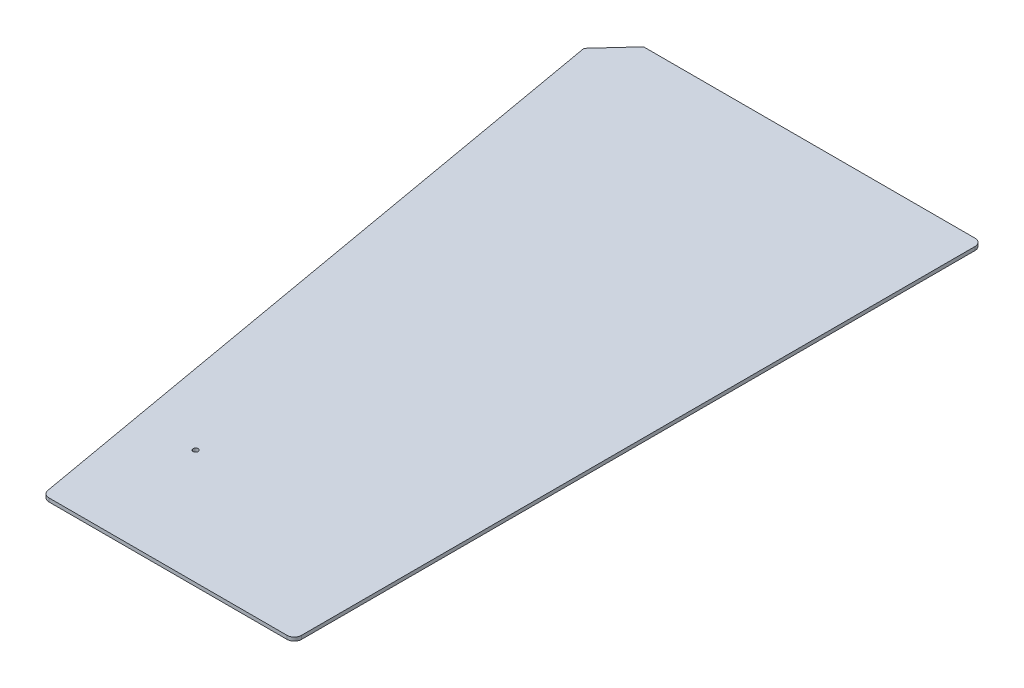
SolidWorks part; units mm, degrees
material "ABS PC"
ref_plane "Front Plane" through (0, 0, 0) normal (0, 0, 1) x (1, 0, 0)
ref_plane "Top Plane" through (0, 0, 0) normal (0, 1, 0) x (1, 0, 0)
ref_plane "Right Plane" through (0, 0, 0) normal (1, 0, 0) x (0, 0, -1)
sketch "Sketch1" plane through (0, 0, 0) normal (0, 1, 0) x (1, 0, 0)
  line L0 (-197.1963, 364.0548) -> (-167.0516, 364.0548) construction
  line L1 (-84.3791, -245.5452) -> (126.6537, -245.5452)
  line L2 (-90.6327, -240.2979) -> (-192.3318, 336.4664)
  line L3 (-167.0516, 364.0548) -> (126.6537, 364.0548)
  line L4 (133.0037, -239.1952) -> (133.0037, 357.7048)
  line L5 (-89.7074, -245.5452) -> (133.0037, 364.0548) construction
  line L6 (-197.1963, 364.0548) -> (133.0037, -245.5452) construction
  line L7 (-192.3318, 336.4664) -> (-197.1963, 364.0548) construction
  line L8 (-167.0516, 364.0548) -> (-192.3318, 336.4664)
  line L9 (-197.1963, 364.0548) -> (-197.1963, -245.5452) construction
  line L10 (-197.1963, -245.5452) -> (-84.3791, -245.5452) construction
  arc A1 (133.0037, -239.1952) -> (126.6537, -245.5452) centre (126.6537, -239.1952) cw
  arc A2 (133.0037, 357.7048) -> (126.6537, 364.0548) centre (126.6537, 357.7048) ccw
  arc A4 (-84.3791, -245.5452) -> (-90.6327, -240.2979) centre (-84.3791, -239.1952) cw
  point P0 (0, 0)
  dimension "D3" = 22.225
  dimension "D5" = 6.35
  dimension "D1" = 609.6
  dimension "D2" = 330.2
  dimension "D4" = 10
  dimension "D6" = 127.5
extrude "Stock to Size" add sketch "Sketch1" along normal blind 3.175
sketch "Sketch3" [suppressed] plane through (0, 0, 0) normal (0, 0, 1) x (1, 0, 0)
  line L1 (-146.05, -361.95) -> (146.05, -361.95)
  line L2 (-152.4, -355.6) -> (-152.4, 355.6)
  line L3 (-146.05, 361.95) -> (146.05, 361.95)
  line L4 (152.4, -355.6) -> (152.4, 355.6)
  line L5 (-152.4, -361.95) -> (152.4, 361.95) construction
  line L6 (-152.4, 361.95) -> (152.4, -361.95) construction
  arc A1 (152.4, -355.6) -> (146.05, -361.95) centre (146.05, -355.6) cw
  arc A2 (152.4, 355.6) -> (146.05, 361.95) centre (146.05, 355.6) ccw
  arc A4 (-146.05, -361.95) -> (-152.4, -355.6) centre (-146.05, -355.6) cw
  arc A5 (-152.4, 355.6) -> (-146.05, 361.95) centre (-146.05, 355.6) cw
  point P0 (0, 0)
  dimension "D5" = 6.35
  dimension "D1" = 723.9
  dimension "D2" = 304.8
  dimension "D4" = 90
extrude "Front Stock" [suppressed] add sketch "Sketch3" along normal blind 3.175
sketch "Sketch2" plane through (0, 3.175, 0) normal (0, 1, 0) x (1, 0, 0)
  line L2 (-192.3318, 336.4664) -> (-90.6327, -240.2979) construction
  line L3 (-84.3791, -245.5452) -> (126.6537, -245.5452) construction
  circle A0 centre (-56.0386, -143.9452) radius 2.286
  dimension "D1" = 4.572
  dimension "D2" = 101.6
  dimension "D3" = 50.8
extrude "Mounting Hole" cut sketch "Sketch2" against normal through all
